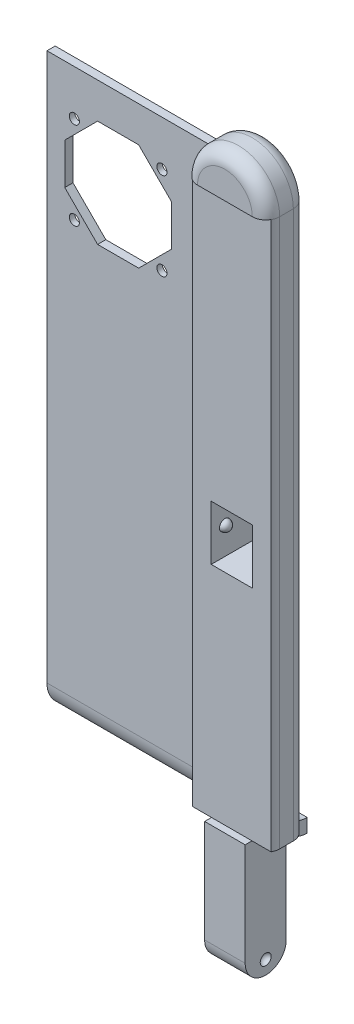
SolidWorks part; units mm, degrees
ref_plane "Front Plane" through (0, 0, 0) normal (0, 0, 1) x (1, 0, 0)
ref_plane "Top Plane" through (0, 0, 0) normal (0, 1, 0) x (1, 0, 0)
ref_plane "Right Plane" through (0, 0, 0) normal (1, 0, 0) x (0, 0, -1)
sketch "Sketch1" plane through (0, 0, 0) normal (0, 0, 1) x (1, 0, 0)
  line L0 (-15, 100) -> (-15, -100)
  line L1 (-15, -100) -> (-7.4, -100)
  line L2 (-7.4, -100) -> (-7.4, -150)
  line L3 (-7.4, -150) -> (7.4, -150)
  line L4 (7.4, -150) -> (7.4, -100)
  line L5 (7.4, -100) -> (15, -100)
  line L6 (15, -100) -> (15, 100)
  arc A0 (15, 100) -> (-15, 100) centre (0, 100) ccw
  dimension "D1" = 15
  dimension "D2" = 250
  dimension "D3" = 50
  dimension "D4" = 15
  dimension "D5" = 14.8
  dimension "D6" = 100
extrude "Boss-Extrude1" add sketch "Sketch1" along normal mid plane 15
fillet "Fillet1" radius 5 6 edges at (-15, 0, -7.5) (0, 115, -7.5) (-15, 0, 7.5) (0, 115, 7.5) (15, 0, -7.5) (15, 0, 7.5)
sketch "Sketch2" plane through (0, 0, 7.5) normal (0, 0, 1) x (1, 0, 0)
  line L0 (-10, 100) -> (-10, -100) construction
  line L1 (-7.5, 0) -> (7.5, 0)
  line L2 (-7.5, 0) -> (-7.5, -20)
  line L3 (-7.5, -20) -> (7.5, -20)
  line L4 (7.5, 0) -> (7.5, -20)
  dimension "D1" = 20
  dimension "D2" = 15
  dimension "D3" = 2.5
extrude "Cut-Extrude1" cut sketch "Sketch2" against normal through all
sketch "Sketch5" plane through (0, 0, 0) normal (0, 0, 1) x (1, 0, 0)
  line L0 (-35.5803, -140) -> (47.5468, -140) construction
  line L1 (-10, -100) -> (-7.4, -100) construction
  line L2 (-7.4, -140) -> (-5.4, -140)
  line L3 (-7.4, -100) -> (-7.4, -150) construction
  line L4 (-7.4, -138) -> (-7.4, -140)
  line L5 (7.4, -140) -> (5.4, -140)
  line L6 (7.4, -150) -> (7.4, -100) construction
  line L7 (7.4, -138) -> (7.4, -140)
  arc A0 (-5.4, -140) -> (-7.4, -138) centre (-7.4, -140) ccw
  arc A1 (5.4, -140) -> (7.4, -138) centre (7.4, -140) cw
  dimension "D1" = 40
  dimension "D2" = 2
  dimension "D3" = 2
revolve "Cut-Revolve1" cut sketch "Sketch5" angle 360 about L0
fillet "Fillet6" radius 5 2 edges at (-7.4, -150, 0) (7.4, -150, 0)
sketch "Sketch7" plane through (7.4, 0, 0) normal (1, 0, 0) x (0, 0, -1)
  line L0 (-7.5, -145) -> (-7.5, -100) construction
  line L1 (7.5, -145) -> (7.5, -100) construction
  line L2 (-7.5, -145) -> (7.5, -145) construction
  line L3 (-7.5, -137.5) -> (-7.5, -150)
  line L4 (-7.5, -150) -> (7.5, -150)
  line L5 (7.5, -150) -> (7.5, -137.5)
  arc A0 (-7.5, -137.5) -> (7.5, -137.5) centre (0, -137.5) ccw
extrude "Cut-Extrude2" cut sketch "Sketch7" against normal through all
sketch "Sketch9" plane through (0, 0, 0) normal (0, 0, 1) x (1, 0, 0)
  line L0 (-32.2513, -10) -> (37.8356, -10) construction
  line L1 (7.5, 0) -> (-7.5, 0) construction
  line L2 (-7.5, -10) -> (-5.5, -10)
  line L3 (-7.5, 0) -> (-7.5, -20) construction
  line L4 (-7.5, -8) -> (-7.5, -10)
  line L5 (7.5, -10) -> (5.5, -10)
  line L6 (7.5, -20) -> (7.5, 0) construction
  line L7 (7.5, -8) -> (7.5, -10)
  arc A0 (-5.5, -10) -> (-7.5, -8) centre (-7.5, -10) ccw
  arc A1 (5.5, -10) -> (7.5, -8) centre (7.5, -10) cw
  dimension "D1" = 10
  dimension "D2" = 2
  dimension "D3" = 2
revolve "Revolve2" add sketch "Sketch9" angle 360 about L0
sketch "Sketch10" plane through (0, 0, 0) normal (1, 0, 0) x (0, 0, -1)
  line L0 (7.5, -100) -> (7.5, 100)
  line L1 (7.5, 100) -> (10.5, 100)
  line L2 (10.5, 100) -> (10.5, -98.5193)
  line L3 (17.5, -105) -> (17.5, -110)
  arc A0 (10.5, -98.5193) -> (17.5, -105) centre (17, -98.5193) ccw
  arc A1 (17.5, -110) -> (7.5, -100) centre (17.5, -100) cw
  dimension "D2" = 10
  dimension "D4" = 6.5
  dimension "D1" = 5
  dimension "D3" = 3
  dimension "D5" = 10
extrude "Boss-Extrude2" add sketch "Sketch10" against normal blind 80
sketch "Sketch11" plane through (0, 0, 0) normal (1, 0, 0) x (0, 0, -1)
  line L0 (17.5, -110) -> (17.5, -105) construction
  line L1 (7.5, 100) -> (7.5, -100) construction
  line L2 (10.5, 100) -> (7.5, 100) construction
  line L3 (10.5, -98.5193) -> (10.5, 100) construction
  line L4 (17.5, -110) -> (17.5, -105)
  line L5 (7.5, 100) -> (7.5, -100)
  line L6 (10.5, 100) -> (7.5, 100)
  line L7 (10.5, -98.5193) -> (10.5, 100)
  arc A0 (10.5, -98.5193) -> (17.5, -105) centre (17, -98.5193) ccw construction
  arc A1 (7.5, -100) -> (17.5, -110) centre (17.5, -100) ccw construction
  arc A2 (10.5, -98.5193) -> (17.5, -105) centre (17, -98.5193) ccw
  arc A3 (7.5, -100) -> (17.5, -110) centre (17.5, -100) ccw
extrude "Boss-Extrude3" add sketch "Sketch11" along normal blind 5
sketch "Sketch12" plane through (0, 0, -10.5) normal (0, 0, -1) x (-1, 0, 0)
  line L0 (7.5, -20) -> (-5, -20) construction
  line L1 (7.5, -20) -> (-5, -20)
  line L2 (7.5, 0) -> (7.5, -20) construction
  line L3 (7.5, 0) -> (-5, 0) construction
  line L4 (80, 100) -> (-5, 100)
  line L5 (-5, 100) -> (-5, -98.5193)
  line L6 (-5, -98.5193) -> (80, -98.5193)
  line L7 (80, -98.5193) -> (80, 100)
  line L9 (-5, 0) -> (-5, -20)
  line L12 (7.5, 0) -> (7.5, -20)
  line L13 (7.5, 0) -> (-5, 0)
  dimension "D1" = 0
extrude "Cut-Extrude3" cut sketch "Sketch12" against normal blind 3
sketch "Sketch13" plane through (-15, 0, 0) normal (-1, 0, 0) x (0, 0, 1)
  line L0 (7.5, -100) -> (5, -100)
  line L1 (2.5, -100) -> (7.5, -100) construction
  line L2 (5, -100) -> (5, 100)
  line L3 (7.5, 100) -> (2.5, 100) construction
  line L4 (5, 100) -> (7.5, 100)
  line L5 (7.5, 100) -> (7.5, -100) construction
  line L6 (7.5, 100) -> (7.5, -100)
extrude "Cut-Extrude4" cut sketch "Sketch13" against normal through all
sketch "Sketch14" plane through (0, 0, -10.5) normal (0, 0, -1) x (-1, 0, 0)
  line L0 (80, -98.5193) -> (-5, -98.5193) construction
  line L1 (80, -98.5193) -> (80, 100) construction
  line L2 (61.5, 86.9807) -> (46.5, 86.9807)
  line L3 (46.5, 86.9807) -> (34.5, 74.9807)
  line L4 (34.5, 74.9807) -> (34.5, 59.9807)
  line L5 (34.5, 59.9807) -> (46.5, 47.9807)
  line L6 (46.5, 47.9807) -> (61.5, 47.9807)
  line L7 (61.5, 47.9807) -> (73.5, 59.9807)
  line L8 (73.5, 59.9807) -> (73.5, 74.9807)
  line L9 (73.5, 74.9807) -> (61.5, 86.9807)
  circle A0 centre (70, 51.4807) radius 1.85
  circle A1 centre (70, 83.4807) radius 1.85
  circle A2 centre (38, 83.4807) radius 1.85
  circle A3 centre (38, 51.4807) radius 1.85
  point P8 (54, 86.9807)
  point P21 (34.5, 67.4807)
  dimension "D4" = 3.7
  dimension "D1" = 150
  dimension "D2" = 32
  dimension "D3" = 32
  dimension "D5" = 10
  dimension "D6" = 15
  dimension "D7" = 16
  dimension "D8" = 16
  dimension "D9" = 39
extrude "Cut-Extrude5" cut sketch "Sketch14" against normal blind 10
sketch "Sketch15" plane through (0, 0, -10.5) normal (0, 0, -1) x (-1, 0, 0)
  circle A0 centre (70, 83.4807) radius 3.25
  circle A1 centre (38, 83.4807) radius 3.25
  circle A2 centre (38, 51.4807) radius 3.25
  circle A3 centre (70, 51.4807) radius 3.25
  dimension "D1" = 6.5
extrude "Cut-Extrude6" cut sketch "Sketch15" against normal blind 1
